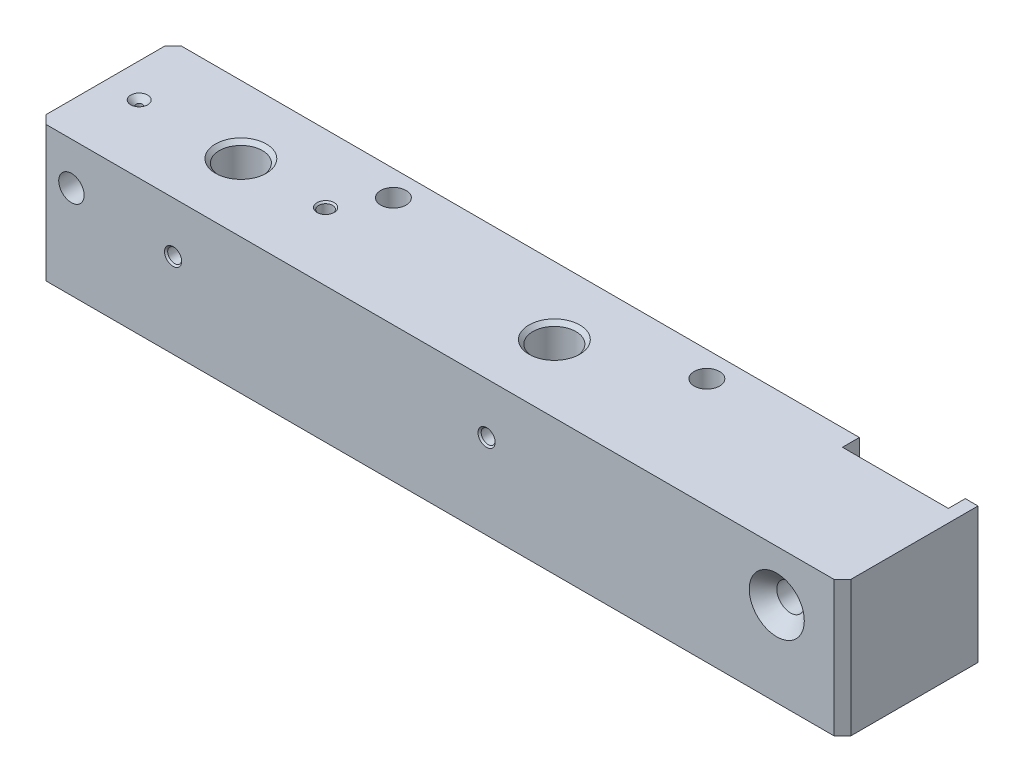
SolidWorks part; units mm, degrees
ref_plane "Front Plane" through (0, 0, 0) normal (0, 0, 1) x (1, 0, 0)
ref_plane "Top Plane" through (0, 0, 0) normal (0, 1, 0) x (1, 0, 0)
ref_plane "Right Plane" through (0, 0, 0) normal (1, 0, 0) x (0, 0, -1)
sketch "Sketch1" plane through (0, 0, 0) normal (0, 0, 1) x (1, 0, 0)
  line L1 (-95, 16) -> (95, 16)
  line L2 (-95, 16) -> (-95, -16)
  line L3 (-95, -16) -> (95, -16)
  line L4 (95, 16) -> (95, -16)
  line L5 (-95, 16) -> (95, -16) construction
  line L6 (-95, -16) -> (95, 16) construction
  point P0 (0, 0)
  dimension "D1" = 190
  dimension "D2" = 32
extrude "Boss-Extrude1" add sketch "Sketch1" along normal mid plane 32
chamfer "Chamfer1" distance 2 angle 45 3 edges at (-95, 0, -16) (95, 0, 16) (-95, 0, 16)
sketch "Sketch2" plane through (0, 16, 0) normal (0, 1, 0) x (1, 0, 0)
  line L0 (95, 16) -> (-93, 16) construction
  line L1 (92, 16) -> (67, 16)
  line L2 (92, 16) -> (92, 12)
  line L3 (92, 12) -> (67, 12)
  line L4 (67, 16) -> (67, 12)
  line L5 (95, -14) -> (95, 16) construction
  dimension "D1" = 25
  dimension "D2" = 4
  dimension "D3" = 3
extrude "Cut-Extrude1" cut sketch "Sketch2" against normal through all
sketch "Sketch3" plane through (0, 16, 0) normal (0, 1, 0) x (1, 0, 0)
  line L0 (-95, 0) -> (95, 0) construction
  line L3 (11, 16) -> (11, -16) construction
  line L4 (67, 16) -> (-93, 16) construction
  line L5 (93, -16) -> (-93, -16) construction
  line L6 (-63, 16) -> (-63, -16) construction
  line L7 (67, 16) -> (67, 12) construction
  line L8 (-95, -14) -> (-95, 14) construction
  line L9 (95, -14) -> (95, 16) construction
  point P16 (67, 14)
  dimension "D1" = 56
  dimension "D2" = 74
hole_wizard "M12 Tapped Hole1" positions "Sketch6" profile "Sketch7" tap size "M12" standard "ISO"
sketch "Sketch6" plane through (0, 16, 0) normal (0, 1, 0) x (1, 0, 0)
  line L0 (-63, 16) -> (-63, -16) construction
  line L1 (11, 16) -> (11, -16) construction
  point P0 (-63, 0)
  point P4 (11, 0)
sketch "Sketch7" plane through (-63, 16, 0) normal (1, 0, 0) x (0, 0, 1)
  line L0 (0, 0) -> (0, 27.0644)
  line L1 (0, 27.0644) -> (5.1, 24)
  line L2 (5.1, 24) -> (5.1, 0.9025)
  line L3 (5.1, 0.9025) -> (6.0025, 0)
  line L5 (6.0025, 0) -> (0, 0)
  line L6 (-5.1, 0.9025) -> (-6.0025, 0) construction
  line L10 (0, 27.0644) -> (-5.1, 24) construction
  line L11 (0, -6.35) -> (0, 107.95) construction
  dimension "Tap Drill Dia." = 10.2
  dimension "Tap Drill Depth" = 24
  dimension "Near C'Sink Dia." = 12.005
  dimension "Near C'Sink Angle" = 90
  dimension "Drill Angle" = 118
cosmetic thread "Hole Thread9" parameters "D1"=24, "D2"=12
cosmetic thread "Hole Thread10" parameters "D1"=24, "D2"=12
sketch "Sketch11" plane through (0, 0, 16) normal (0, 0, 1) x (1, 0, 0)
  line L0 (-63, -8) -> (-63, 16) construction
  line L1 (-57.9, -8) -> (-68.1, -8) construction
  line L2 (-95, 16) -> (95, 16) construction
  line L3 (11, -8) -> (11, 16) construction
  line L4 (16.1, -8) -> (5.9, -8) construction
  line L5 (-63, 4) -> (11, 4) construction
hole_wizard "M4 Tapped Hole2" positions "3DSketch1" profile "Sketch12" tap size "M4" standard "ISO"
sketch3d "3DSketch1"
  point P0 (-63, 4, 16)
  point P3 (11, 4, 16)
sketch "Sketch12" plane through (-63, 4, 16) normal (1, 0, 0) x (0, -1, 0)
  line L0 (0, 0) -> (0, 12.4914)
  line L1 (0, 12.4914) -> (1.65, 11.5)
  line L2 (1.65, 11.5) -> (1.65, 0.375)
  line L3 (1.65, 0.375) -> (2.025, 0)
  line L5 (2.025, 0) -> (0, 0)
  line L6 (-1.65, 0.375) -> (-2.025, 0) construction
  line L10 (0, 12.4914) -> (-1.65, 11.5) construction
  line L11 (0, -6.35) -> (0, 107.95) construction
  dimension "Tap Drill Dia." = 3.3
  dimension "Tap Drill Depth" = 11.5
  dimension "Near C'Sink Dia." = 4.05
  dimension "Near C'Sink Angle" = 90
  dimension "Drill Angle" = 118
cosmetic thread "Hole Thread11" parameters "D1"=8, "D2"=4
cosmetic thread "Hole Thread12" parameters "D1"=8, "D2"=4
sketch "Sketch13" plane through (0, 0, 16) normal (0, 0, 1) x (1, 0, 0)
  line L0 (79.5, -16) -> (79.5, 4) construction
  line L1 (-93, -16) -> (93, -16) construction
  line L2 (79.5, 4) -> (93, 4) construction
  line L3 (93, -16) -> (93, 16) construction
  line L4 (95, 16) -> (95, -16) construction
  dimension "D1" = 15.5
  dimension "D2" = 20
hole_wizard "CSK for M10 Countersunk Flat Head Screw1" positions "Sketch14" profile "Sketch15" countersink size "M10" standard "ISO" end condition through all
sketch "Sketch14" plane through (0, 0, 16) normal (0, 0, 1) x (1, 0, 0)
  point P0 (79.5, 4)
sketch "Sketch15" plane through (79.5, 4, 16) normal (1, 0, 0) x (0, -1, 0)
  line L0 (0, 0) -> (0, 32)
  line L1 (0, 32) -> (3.25, 32)
  line L2 (3.25, 32) -> (3.25, 3.25)
  line L3 (3.25, 3.25) -> (6.5, 0)
  line L5 (6.5, 0) -> (0, 0)
  line L6 (-3.25, 3.25) -> (-6.5, 0) construction
  line L11 (0, -6.35) -> (0, 107.95) construction
  dimension "Thru Hole Dia." = 6.5
  dimension "Thru Hole Depth" = 32
  dimension "Near C'Sink Dia." = 13
  dimension "Near C'Sink Angle" = 90
sketch "Sketch16" plane through (0, 0, 16) normal (0, 0, 1) x (1, 0, 0)
  line L0 (-63, 4) -> (-87, 4) construction
  line L1 (-87, 4) -> (-87, 23.211) construction
  line L2 (-93, -16) -> (93, -16) construction
  circle A0 centre (-87, 6) radius 3
  dimension "D3" = 6
  dimension "D1" = 22
  dimension "D2" = 24
extrude "Cut-Extrude2" cut sketch "Sketch16" against normal through all
hole_wizard "CSK for M4 Countersunk Flat Head Screw1" positions "Sketch18" profile "Sketch19" countersink size "M4" standard "ISO"
sketch "Sketch18" plane through (0, 16, 0) normal (0, 1, 0) x (1, 0, 0)
  line L0 (-95, 0) -> (95, 0) construction
  point P0 (-87, 0)
  dimension "D1" = 24
sketch "Sketch19" plane through (-87, 16, 0) normal (1, 0, 0) x (0, 0, 1)
  line L0 (0, 0) -> (0, 10.4506)
  line L1 (0, 10.4506) -> (0.75, 10)
  line L2 (0.75, 10) -> (0.75, 1.25)
  line L3 (0.75, 1.25) -> (2, 0)
  line L5 (2, 0) -> (0, 0)
  line L6 (-0.75, 1.25) -> (-2, 0) construction
  line L10 (0, 10.4506) -> (-0.75, 10) construction
  line L11 (0, -6.35) -> (0, 107.95) construction
  dimension "Hole Dia." = 1.5
  dimension "Hole Depth" = 10
  dimension "Near C'Sink Dia." = 4
  dimension "Near C'Sink Angle" = 90
  dimension "Drill Angle" = 118
hole_wizard "M4 Tapped Hole3" positions "Sketch22" profile "Sketch23" tap size "M4" standard "ISO"
sketch "Sketch22" plane through (0, 16, 0) normal (0, 1, 0) x (1, 0, 0)
  line L0 (-95, 0) -> (95, 0) construction
  point P0 (-43, 0)
  dimension "D1" = 20
sketch "Sketch23" plane through (-43, 16, 0) normal (1, 0, 0) x (0, 0, 1)
  line L0 (0, 0) -> (0, 16.9914)
  line L1 (0, 16.9914) -> (1.65, 16)
  line L2 (1.65, 16) -> (1.65, 0.375)
  line L3 (1.65, 0.375) -> (2.025, 0)
  line L5 (2.025, 0) -> (0, 0)
  line L6 (-1.65, 0.375) -> (-2.025, 0) construction
  line L10 (0, 16.9914) -> (-1.65, 16) construction
  line L11 (0, -6.35) -> (0, 107.95) construction
  dimension "Tap Drill Dia." = 3.3
  dimension "Tap Drill Depth" = 16
  dimension "Near C'Sink Dia." = 4.05
  dimension "Near C'Sink Angle" = 90
  dimension "Drill Angle" = 118
cosmetic thread "Hole Thread13" parameters "D1"=8, "D2"=4
sketch "Sketch24" plane through (0, 16, 0) normal (0, 1, 0) x (1, 0, 0)
  line L0 (-95, -14) -> (-95, 14) construction
  line L1 (67, 16) -> (-93, 16) construction
  circle A0 centre (-37, 10) radius 3
  circle A1 centre (37, 10) radius 3
  dimension "D4" = 6
  dimension "D1" = 74
  dimension "D2" = 58
  dimension "D3" = 6
extrude "Cut-Extrude4" cut sketch "Sketch24" against normal through all contours A0 | A1
